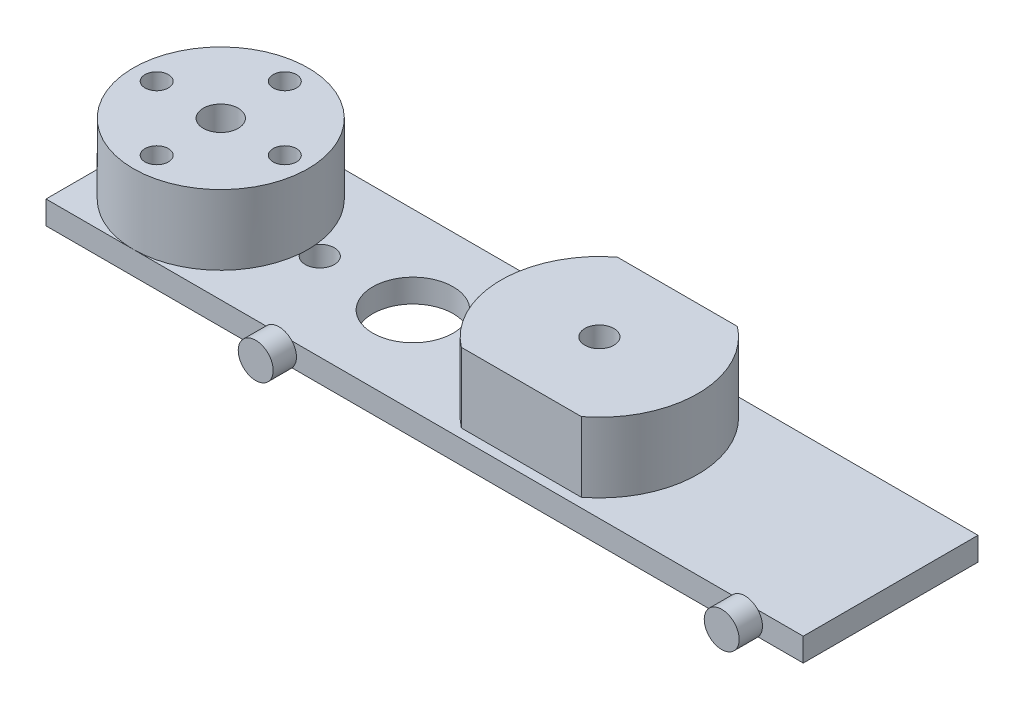
SolidWorks part; units mm, degrees
ref_plane "前视基准面" through (0, 0, 0) normal (0, 0, 1) x (1, 0, 0)
ref_plane "上视基准面" through (0, 0, 0) normal (0, 1, 0) x (1, 0, 0)
ref_plane "右视基准面" through (0, 0, 0) normal (1, 0, 0) x (0, 0, -1)
other "Configuration Table"
sketch "草图1" plane through (0, 0, 0) normal (0, 1, 0) x (1, 0, 0)
  line L0 (0, 7.5) -> (0, -7.5) construction
  line L1 (-25, 7.5) -> (25, 7.5)
  line L2 (-25, 7.5) -> (-25, -7.5)
  line L3 (-25, -7.5) -> (25, -7.5)
  line L4 (25, 7.5) -> (25, -7.5)
  line L5 (-25, 0) -> (25, 0) construction
  line L7 (-25, -7.5) -> (-40, -7.5)
  line L10 (-25, -7.5) -> (-25, 7.5)
  line L11 (-25, 7.5) -> (-40, 7.5)
  line L12 (-40, -7.5) -> (-40, 7.5)
  line L14 (-25, 7.5) -> (-40, 7.5)
  dimension "D1" = 50
  dimension "D2" = 15
  dimension "D6" = 15
  dimension "D7" = 15
extrude "凸台-拉伸1" add sketch "草图1" along normal blind 2 contours L11 L2 | L2 L1 L4 L3 | L10 L7 L12 L11 region at (-32.5, 0, 0)
sketch "草图2" plane through (0, 0, 0) normal (0, 1, 0) x (1, 0, 0)
  line L0 (0, 7.5) -> (0, -7.5) construction
  line L1 (25, 7.5) -> (-40, 7.5) construction
  line L2 (-32.5, 7.5) -> (-32.5, -7.5) construction
  line L3 (-40, -7.5) -> (-40, 7.5) construction
  line L4 (-25, 7.5) -> (-25, -7.5) construction
  line L6 (-25, -7.5) -> (25, -7.5) construction
  line L10 (-40, 0) -> (-25, 0) construction
  line L14 (-40, -7.5) -> (25, -7.5) construction
  circle A2 centre (0, 0) radius 1.25
  circle A3 centre (16, 0) radius 4.1
  circle A4 centre (16, 0) radius 3.45
  circle A5 centre (-16, 0) radius 4.1
  circle A6 centre (-16, 0) radius 3.45
  circle A8 centre (24, 0) radius 1.25
  circle A9 centre (-24, 0) radius 1.25
  circle A11 centre (-32.5, 0) radius 1.5
  circle A12 centre (-27, 0) radius 1
  circle A13 centre (-32.5, -5.5) radius 1
  circle A14 centre (-38, 0) radius 1
  circle A15 centre (-32.5, 5.5) radius 1
  point P36 (0, -7.5)
  dimension "D3" = 2.5
  dimension "D4" = 6.9
  dimension "D5" = 8.2
  dimension "D7" = 15
  dimension "D8" = 2.5
  dimension "D11" = 3
  dimension "D12" = 2
  dimension "D2" = 7.5
  dimension "D6" = 16
  dimension "D10" = 8
  dimension "D13" = 5.5
  dimension "D17" = 7.5
  dimension "D14" = 4
extrude "切除-拉伸1" cut sketch "草图2" along normal up to surface (2 mm away) contours A2 | A9 | A6 | A14 | A11 | A13 | A12 | A15 up to face at (-7.5, 2, 0)
sketch "草图4" plane through (0, 0, 7.5) normal (0, 0, 1) x (1, 0, 0)
  line L0 (25, 1) -> (-40, 1) construction
  line L1 (25, 2) -> (25, 0) construction
  line L2 (-40, 2) -> (-40, 0) construction
  line L3 (0, 0) -> (0, 2) construction
  line L5 (25, 2) -> (25, 0) construction
  line L6 (-40, 2) -> (25, 2) construction
  circle A0 centre (20, 1) radius 1.5
  circle A1 centre (-20, 1) radius 1.5
  dimension "D1" = 3
  dimension "D2" = 3
  dimension "D3" = 20
  dimension "D4" = 20
  dimension "D5" = 25
extrude "凸台-拉伸2" add sketch "草图4" along normal blind 2
sketch "草图5" plane through (0, 2, 0) normal (0, 1, 0) x (1, 0, 0)
  line L0 (0, 0) -> (0, 4.126) construction
  line L1 (4.9054, -6) -> (-4.9054, -6)
  line L2 (-4.7026, 0) -> (-2.9861, 0) construction
  line L3 (4.9054, 6) -> (-4.9054, 6)
  line L4 (5.149, -6.7) -> (-5.149, -6.7)
  line L5 (5.149, 6.7) -> (-5.149, 6.7)
  arc A0 (-4.9054, 6) -> (-4.9054, -6) centre (0, 0) ccw
  arc A1 (4.9054, -6) -> (4.9054, 6) centre (0, 0) ccw
  arc A2 (-5.149, 6.7) -> (-5.149, -6.7) centre (0, 0) ccw
  arc A3 (5.149, -6.7) -> (5.149, 6.7) centre (0, 0) ccw
  circle A4 centre (-32.5, 0) radius 7.5
  circle A5 centre (-32.5, 0) radius 7.2
  point P14 (0, -6)
  point P15 (0, 6)
  point P21 (0, -6.7)
  point P22 (0, 6.7)
  circle M9 centre (0, 0) radius 1.25
  dimension "D1" = 15.5
  dimension "D3" = 16.9
  dimension "D5" = 14.4
  dimension "D6" = 15
  dimension "D2" = 12
  dimension "D4" = 13.4
extrude "凸台-拉伸3" add sketch "草图5" along normal blind 6
extrude "凸台-拉伸4" add sketch "草图5<8>" along direction (0, 1, 0) on the side of the normal up to surface (6 mm away) contours L1 A1 L3 A0 M9 | A5 region at (0, 2, 5.804) up to face at (0, 8, 0)
sketch "草图5<8>" plane through (0, 2, 0) normal (0, 1, 0) x (1, 0, 0) same geometry as "草图5"
extrude "切除-拉伸2" cut sketch "草图5<11>" against normal through all and the other way offset from surface 2.5 contours L1 A1 L3 A0 M9 | A5 region at (0, 2, 5.804) other way up to face at (0, 8, 0)
sketch "草图5<11>" plane through (0, 2, 0) normal (0, 1, 0) x (1, 0, 0) same geometry as "草图5"
extrude "切除-拉伸3" cut sketch "草图2<3>" along normal up to surface (8 mm away) contours A11 | A15 | A14 | A13 | A12 region at (-32.5, 0, 0) region at (-32.5, 0, 5.5) region at (-38, 0, 0) region at (-32.5, 0, -5.5) up to face at (-32.5, 8, 7.5)
sketch "草图2<3>" plane through (0, 0, 0) normal (0, 1, 0) x (1, 0, 0) same geometry as "草图2"
